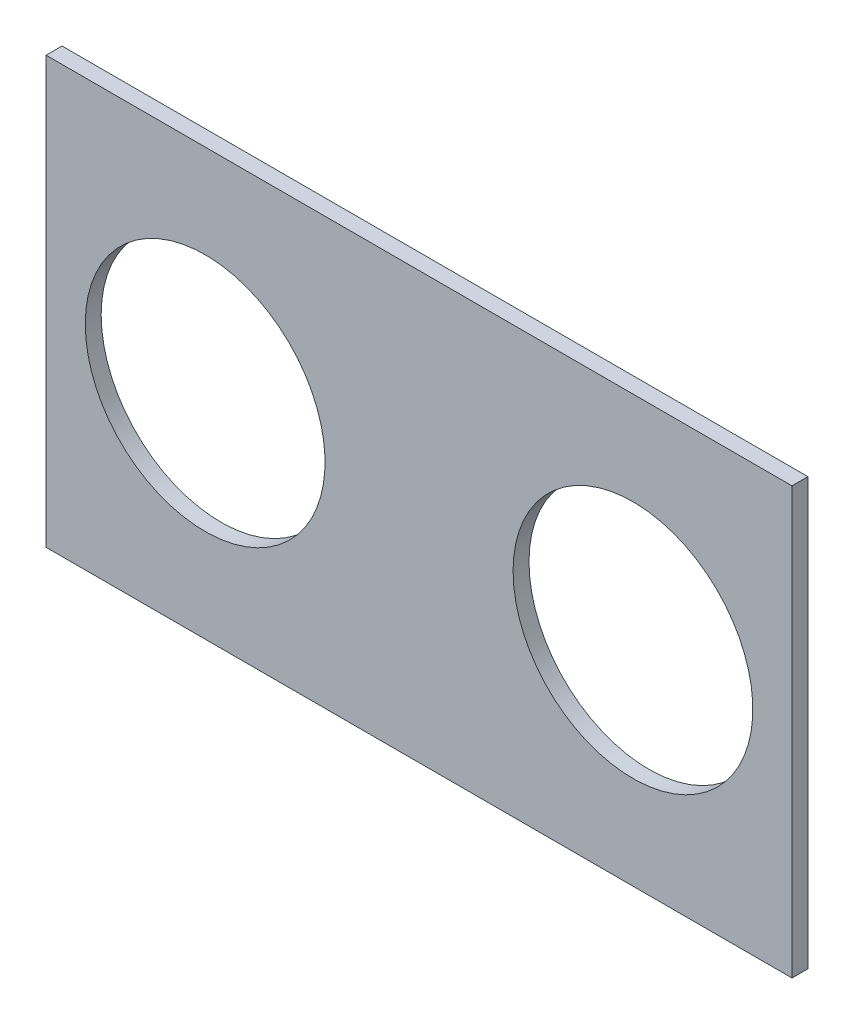
SolidWorks part; units mm, degrees
material "Plain Carbon Steel"
ref_plane "Front Plane" through (0, 0, 0) normal (0, 0, 1) x (1, 0, 0)
ref_plane "Top Plane" through (0, 0, 0) normal (0, 1, 0) x (1, 0, 0)
ref_plane "Right Plane" through (0, 0, 0) normal (1, 0, 0) x (0, 0, -1)
sketch "Sketch1" plane through (0, 0, 0) normal (0, 0, 1) x (1, 0, 0)
  line L0 (-18.9548, 0) -> (69.9452, 0) construction
  line L1 (-18.9548, 25.4) -> (69.9452, 25.4)
  line L2 (-18.9548, 25.4) -> (-18.9547, -25.4)
  line L3 (-18.9547, -25.4) -> (69.9452, -25.4)
  line L4 (69.9452, 25.4) -> (69.9452, -25.4)
  line L5 (25.4953, 25.4) -> (25.4953, -25.4) construction
  circle A2 centre (0, 0) radius 14.2875
  circle A3 centre (50.9905, 0) radius 14.2875
  circle A4 centre (0, 0) radius 14.2875 construction
  circle A5 centre (50.9905, 0) radius 14.2875 construction
  dimension "D1" = 50.8
  dimension "D2" = 88.9
extrude "Boss-Extrude1" add sketch "Sketch1" along normal blind 1.8974
